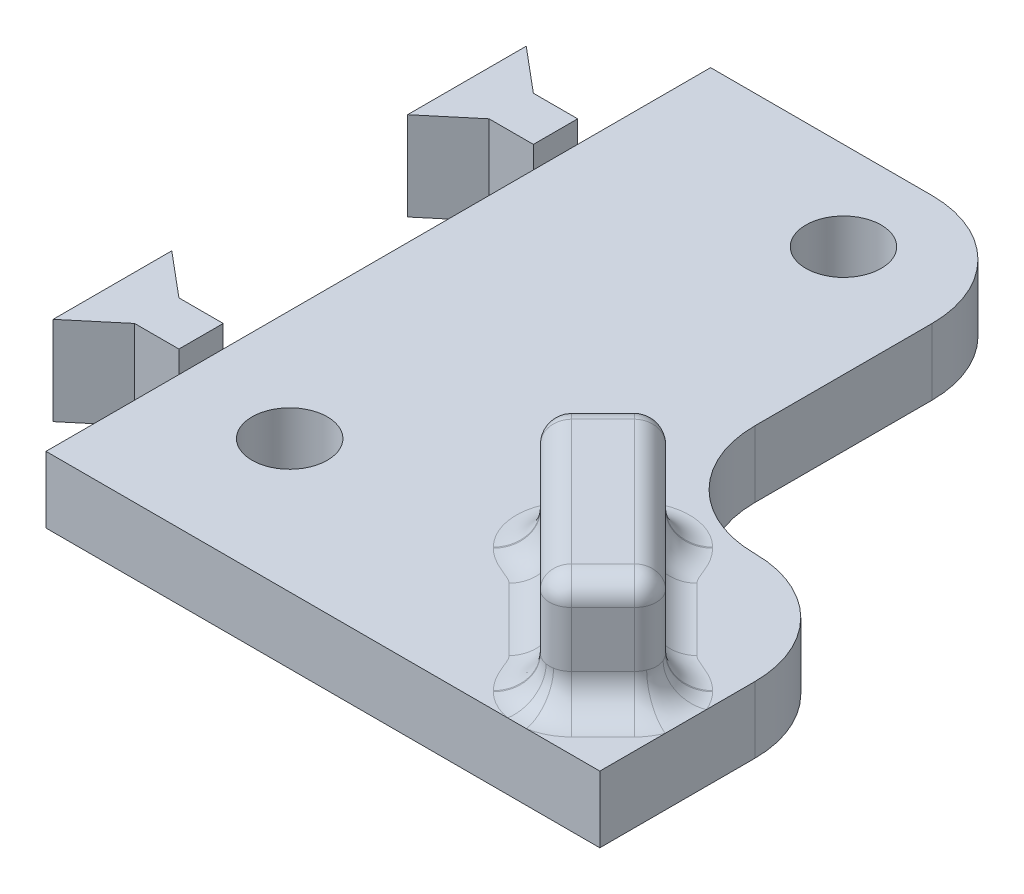
SolidWorks part; units mm, degrees
ref_plane "Front Plane" through (0, 0, 0) normal (0, 0, 1) x (1, 0, 0)
ref_plane "Top Plane" through (0, 0, 0) normal (0, 1, 0) x (1, 0, 0)
ref_plane "Right Plane" through (0, 0, 0) normal (1, 0, 0) x (0, 0, -1)
sketch "Sketch1" plane through (0, 0, 0) normal (0, 1, 0) x (1, 0, 0)
  line L1 (20, -6) -> (-5, -6)
  line L2 (20, -6) -> (20, 24)
  line L3 (20, 24) -> (-5, 24)
  line L4 (-5, -6) -> (-5, 24)
  dimension "D1" = 20
  dimension "D2" = 5
  dimension "D3" = 6
  dimension "D4" = 24
extrude "Boss-Extrude1" add sketch "Sketch1" along normal blind 3
sketch "Sketch2" plane through (0, 0, 0) normal (0, 1, 0) x (1, 0, 0)
  circle A0 centre (0, 0) radius 1.7
  circle A1 centre (5, 20) radius 1.7
  dimension "D1" = 3.4
  dimension "D2" = 5
  dimension "D3" = 20
extrude "Cut-Extrude1" cut sketch "Sketch2" along normal up to next
sketch "Sketch7" plane through (0, 3, 0) normal (0, 1, 0) x (1, 0, 0)
  line L1 (20, 24) -> (10, 24)
  line L2 (20, 24) -> (20, 6)
  line L3 (20, 6) -> (10, 6)
  line L4 (10, 24) -> (10, 6)
  dimension "D1" = 10
  dimension "D2" = 18
extrude "Cut-Extrude3" cut sketch "Sketch7" against normal up to next
fillet "Fillet4" radius 5 3 edges at (20, 1.5, -6) (10, 1.5, -6) (10, 1.5, -24)
sketch "Sketch3" plane through (0, 3, 0) normal (0, 1, 0) x (1, 0, 0)
  line L0 (12.0208, 4.9497) -> (9.1924, 2.1213)
  line L1 (12.0208, 4.9497) -> (19.0919, -2.1213)
  line L2 (9.1924, 2.1213) -> (16.2635, -4.9497)
  line L3 (19.0919, -2.1213) -> (16.2635, -4.9497)
  line L4 (0, -4.4) -> (0, 4.4) construction
  dimension "D1" = 45
  dimension "D2" = 4
  dimension "D3" = 10
  dimension "D4" = 8
  dimension "D5" = 5
extrude "Boss-Extrude2" add sketch "Sketch3" along normal blind 5
sketch "Sketch4" plane through (5.6569, 0, -5.6569) normal (-0.7071, 0, 0.7071) x (0.7071, 0, 0.7071)
  line L0 (5, 8) -> (15, 8) construction
  line L1 (7, 6) -> (13, 6)
  line L2 (7, 6) -> (7, 4)
  line L3 (7, 4) -> (13, 4)
  line L4 (13, 6) -> (13, 4)
  line L5 (15, 8) -> (15, 3) construction
  line L6 (5, 8) -> (5, 3) construction
  line L8 (5, 3) -> (15, 3) construction
  dimension "D1" = 2
  dimension "D2" = 2
  dimension "D3" = 2
  dimension "D4" = 1
extrude "Cut-Extrude2" cut sketch "Sketch4" against normal up to next
fillet "Fillet2" radius 1 16 edges at (12.0208, 6, -2.1213) (12.7279, 6, 1.4142) (16.2635, 6, 2.1213) (15.5563, 6, -1.4142) (16.2635, 4, 2.1213) (12.7279, 4, 1.4142) (12.0208, 4, -2.1213) (15.5563, 4, -1.4142) (17.6777, 8, 3.5355) (12.7279, 8, 1.4142) (10.6066, 8, -3.5355) (15.5563, 8, -1.4142) (12.0208, 5.5, -4.9497) (9.1924, 5.5, -2.1213) (19.0919, 5.5, 2.1213) (16.2635, 5.5, 4.9497)
fillet "Fillet3" radius 1.5 12 edges at (18.6777, 3, 2.1213) (15.5563, 3, -1.4142) (13.435, 3, -3.5355) (12.0208, 3, -4.5355) (10.6066, 3, -3.5355) (9.6066, 3, -2.1213) (10.6066, 3, -0.7071) (17.6777, 3, 3.5355) (12.7279, 3, 1.4142) (17.6777, 3, 0.7071) (16.2635, 3, 4.5355) (14.8492, 3, 3.5355)
sketch "Sketch5" plane through (0, 0, 0) normal (0, 1, 0) x (1, 0, 0)
  line L0 (-5, 24) -> (-5, -6) construction
  line L1 (-5, 2) -> (-7, 2)
  line L2 (-5, 2) -> (-5, 0)
  line L3 (-5, 0) -> (-7, 0)
  line L5 (-7, 2) -> (-9, 3.6782)
  line L6 (-9, 3.6782) -> (-9, -1.6782)
  line L7 (-9, -1.6782) -> (-7, 0)
  line L8 (-5, 18) -> (-7, 18)
  line L9 (-7, 18) -> (-9, 19.6782)
  line L10 (-9, 19.6782) -> (-9, 14.3218)
  line L11 (-9, 14.3218) -> (-7, 16)
  line L12 (-5, 16) -> (-7, 16)
  line L13 (-5, 18) -> (-5, 16)
  point P6 (-9, 1)
  point P9 (-5, 1)
  point P13 (-5, 17)
  dimension "D1" = 140
  dimension "D2" = 140
  dimension "D3" = 2
  dimension "D4" = 2
  dimension "D5" = 2
  dimension "D6" = 7
  dimension "D8" = 16
  dimension "D7" = 2
extrude "Boss-Extrude3" add sketch "Sketch5" along normal blind 4
equation "\"D2@Sketch5\"=\"D1@Sketch5\""
